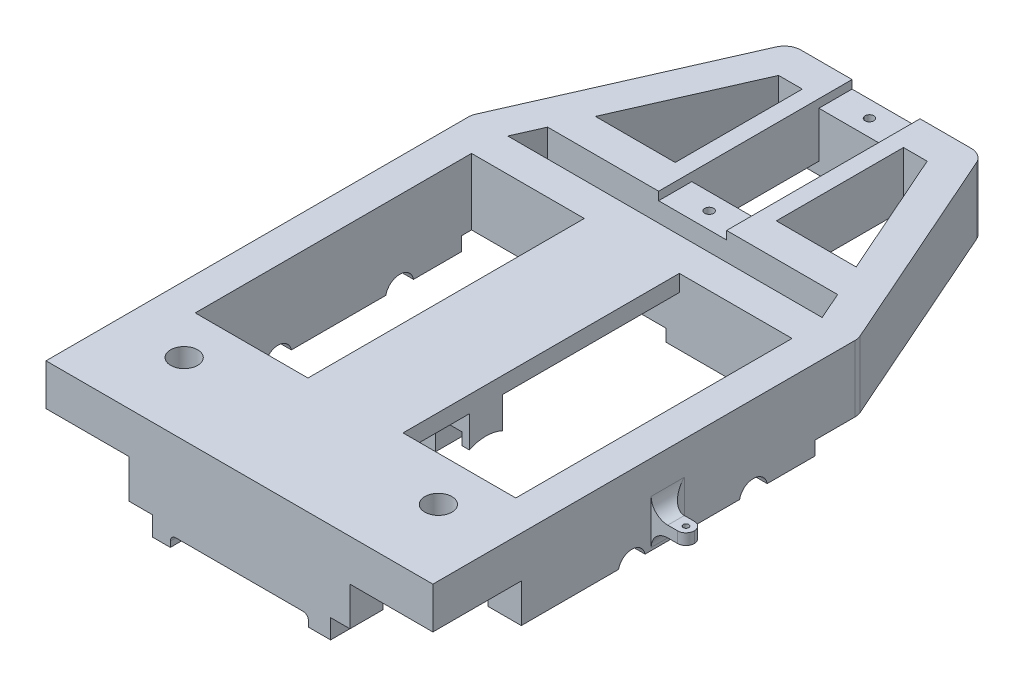
SolidWorks part; units mm, degrees
ref_plane "Front Plane" through (0, 0, 0) normal (0, 0, 1) x (1, 0, 0)
ref_plane "Top Plane" through (0, 0, 0) normal (0, 1, 0) x (1, 0, 0)
ref_plane "Right Plane" through (0, 0, 0) normal (1, 0, 0) x (0, 0, -1)
sketch "Sketch1" plane through (0, 0, 0) normal (0, 1, 0) x (1, 0, 0)
  line L0 (-35, 38.5) -> (-17.3529, 78.5)
  line L1 (-29, 32.5) -> (29, 32.5)
  line L2 (-29, 32.5) -> (-29, -32.5)
  line L3 (-29, -32.5) -> (29, -32.5)
  line L4 (29, 32.5) -> (29, -32.5)
  line L5 (-29, 32.5) -> (29, -32.5) construction
  line L6 (-29, -32.5) -> (29, 32.5) construction
  line L7 (-28.442, 38.5) -> (28.442, 38.5)
  line L8 (-35, 38.5) -> (-35, -38.5)
  line L9 (-35, -38.5) -> (35, -38.5)
  line L10 (35, 38.5) -> (35, -38.5)
  line L11 (-35, 38.5) -> (35, -38.5) construction
  line L12 (-35, -38.5) -> (35, 38.5) construction
  line L13 (-17.3529, 78.5) -> (17.3529, 78.5)
  line L14 (17.3529, 78.5) -> (35, 38.5)
  line L15 (-28.442, 38.5) -> (-13.442, 72.5)
  line L16 (-13.442, 72.5) -> (13.442, 72.5)
  line L17 (13.442, 72.5) -> (28.442, 38.5)
  point P0 (0, 0)
  point P6 (0, 0)
  point P15 (0, 72.5)
  point P18 (0, 38.5)
  dimension "D1" = 58
  dimension "D2" = 6
  dimension "D3" = 6
  dimension "D4" = 65
  dimension "D5" = 40
  dimension "D6" = 6
  dimension "D7" = 6
  dimension "D8" = 6
  dimension "D9" = 34
  dimension "D10" = 15
  dimension "D11" = 6
  dimension "D12" = 6
extrude "Boss-Extrude1" add sketch "Sketch1" along normal blind 30
ref_plane "Plane1" through (0, 0, 5.5) normal (0, 0, 1) x (1, 0, 0)
ref_plane "Plane2" through (0, 15, 0) normal (0, -1, 0) x (-1, 0, 0)
sketch "Sketch7" plane through (0, 0, -32.5) normal (0, 0, 1) x (1, 0, 0)
  line L0 (-35, 30) -> (35, 30) construction
  line L1 (-8.6, 30) -> (8.6, 30)
  line L2 (-8.6, 30) -> (-8.6, 27)
  line L3 (-8.6, 27) -> (8.6, 27)
  line L4 (8.6, 30) -> (8.6, 27)
  line L6 (-35, 30) -> (-35, 0) construction
  point P6 (0, 30)
  dimension "D1" = 3
  dimension "D2" = 17.2
  dimension "D3" = 35
sketch "Sketch8" plane through (0, 0, 5.5) normal (0, 0, 1) x (1, 0, 0)
  line L0 (-8.6, 30) -> (8.6, 30) construction
  line L1 (-8.6, 30) -> (8.6, 30)
  line L2 (-8.6, 30) -> (-8.6, 27)
  line L3 (-8.6, 27) -> (8.6, 27)
  line L4 (8.6, 30) -> (8.6, 27)
  line L5 (-8.6, 27) -> (8.6, 27) construction
sketch "Sketch9" plane through (0, 30, 0) normal (0, 1, 0) x (1, 0, 0)
  line L0 (10, 32.5) -> (2.5, -5.5)
  line L1 (-8.6, 32.5) -> (8.6, 32.5) construction
  line L2 (-8.6, -5.5) -> (8.6, -5.5) construction
  line L3 (-16.5058, -5.5) -> (16.5058, -5.5) construction
  line L4 (-10, 32.5) -> (-2.5, -5.5)
loft "Loft3" add profiles "Sketch7", "Sketch8"
mirror "Mirror3" about plane through (0, 15, 0) normal (0, -1, 0) of "Loft3"
sketch "Sketch10" plane through (0, 27, 0) normal (0, -1, 0) x (1, 0, 0)
  line L0 (-8.6, -32.5) -> (8.6, -32.5) construction
  line L1 (-2.5, 5.5) -> (2.5, 5.5)
  line L2 (-2.5, 5.5) -> (-2.5, -0.5)
  line L3 (-2.5, -0.5) -> (2.5, -0.5)
  line L4 (2.5, 5.5) -> (2.5, -0.5)
  line L6 (-8.6, 5.5) -> (8.6, 5.5) construction
  point P5 (2.5, 2.5)
  point P10 (0, 5.5)
  point P11 (0, 5.5)
  dimension "D1" = 5
  dimension "D2" = 35
  dimension "D3" = 0
  dimension "D4" = 0
extrude "Boss-Extrude3" add sketch "Sketch10" along normal up to next
sketch "Sketch2" plane through (35, 0, 0) normal (1, 0, 0) x (0, 0, -1)
  line L0 (38.5, 30) -> (38.5, 0) construction
  line L1 (-38.5, 30) -> (38.5, 30) construction
  circle A0 centre (-2.5, 15) radius 2.45
  circle A1 centre (19.5, 15) radius 2.55
  dimension "D2" = 15
  dimension "D3" = 4.9
  dimension "D5" = 5.1
  dimension "D1" = 19
  dimension "D4" = 22
extrude "Cut-Extrude1" cut sketch "Sketch2" against normal up to next
sketch "Sketch3" plane through (0, 0, -38.5) normal (0, 0, -1) x (-1, 0, 0)
  line L1 (-6.2, 20.2) -> (6.2, 20.2)
  line L2 (-6.2, 20.2) -> (-6.2, 9.8)
  line L3 (-6.2, 9.8) -> (6.2, 9.8)
  line L4 (6.2, 20.2) -> (6.2, 9.8)
  line L5 (-6.2, 20.2) -> (6.2, 9.8) construction
  line L6 (-6.2, 9.8) -> (6.2, 20.2) construction
  line L7 (-17.3529, 0) -> (17.3529, 0) construction
  line L9 (35, 30) -> (35, 0) construction
  point P0 (0, 15)
  dimension "D1" = 10.4
  dimension "D2" = 12.4
  dimension "D3" = 35
  dimension "D4" = 15
extrude "Cut-Extrude2" cut sketch "Sketch3" against normal up to next
sketch "Sketch11" plane through (35, 0, 0) normal (1, 0, 0) x (0, 0, -1)
  line L0 (-2.5, 15) -> (72.7738, 15) construction
  line L1 (1, 19) -> (4, 19)
  line L2 (1, 19) -> (1, 21)
  line L3 (1, 21) -> (4, 21)
  line L4 (4, 19) -> (4, 21)
  line L5 (4, 11) -> (4, 9)
  line L6 (1, 9) -> (4, 9)
  line L7 (1, 11) -> (1, 9)
  line L8 (1, 11) -> (4, 11)
  point P7 (2.5, 19)
  dimension "D1" = 3
  dimension "D2" = 2
  dimension "D3" = 6
  dimension "D4" = 5
extrude "Boss-Extrude4" add sketch "Sketch11" along normal blind 6.3
fillet "Fillet3" radius 1.5 4 edges at (41.3, 10, -1) (41.3, 10, -4) (41.3, 20, -1) (41.3, 20, -4)
sketch "Sketch12" plane through (0, 21, 0) normal (0, 1, 0) x (1, 0, 0)
  circle A0 centre (39.8, 2.5) radius 0.5
extrude "Cut-Extrude3" cut sketch "Sketch12" against normal through all
ref_plane "Plane3" through (0, 0, 0) normal (1, 0, 0) x (0, 0, -1)
mirror "Mirror1" about plane through (0, 0, 0) normal (1, 0, 0) of "Cut-Extrude1", "Boss-Extrude4", "Fillet3", "Cut-Extrude3"
sketch "Sketch13" plane through (-29, 0, 0) normal (1, 0, 0) x (0, 0, -1)
  line L1 (-32.5, 30) -> (-17.5, 30)
  line L2 (-32.5, 30) -> (-32.5, 24)
  line L3 (-32.5, 24) -> (-17.5, 24)
  line L4 (-17.5, 30) -> (-17.5, 24)
  dimension "D1" = 6
  dimension "D2" = 15
extrude "Boss-Extrude5" add sketch "Sketch13" along normal up to next
sketch "Sketch17" plane through (-29, 0, 0) normal (1, 0, 0) x (0, 0, -1)
  line L0 (32.5, 0) -> (-32.5, 0) construction
  line L1 (-32.5, 0) -> (-17.5, 0)
  line L2 (-32.5, 0) -> (-32.5, 14)
  line L3 (-32.5, 14) -> (-17.5, 14)
  line L4 (-17.5, 0) -> (-17.5, 14)
  dimension "D1" = 14
  dimension "D2" = 15
extrude "Boss-Extrude6" add sketch "Sketch17" along normal up to next
sketch "Sketch14" plane through (0, 30, 0) normal (0, 1, 0) x (1, 0, 0)
  line L0 (-35, 38.5) -> (-35, -38.5) construction
  line L1 (35, -38.5) -> (35, 38.5) construction
  line L2 (-35, -38.5) -> (35, -38.5) construction
  circle A0 centre (-23, -25.5) radius 2.45
  circle A1 centre (23, -25.5) radius 2.45
  dimension "D5" = 4.9
  dimension "D6" = 4.9
  dimension "D1" = 12
  dimension "D2" = 12
  dimension "D3" = 13
  dimension "D4" = 0
extrude "Cut-Extrude4" cut sketch "Sketch14" against normal through all
sketch "Sketch16" plane through (35, 0, 0) normal (1, 0, 0) x (0, 0, -1)
  line L0 (-38.5, 30) -> (-38.5, 0) construction
  line L7 (-38.5, 22.5) -> (-22.5, 22.5)
  line L8 (-38.5, 22.5) -> (-38.5, 15.5)
  line L9 (-38.5, 15.5) -> (-22.5, 15.5)
  line L10 (-22.5, 22.5) -> (-22.5, 15.5)
  line L11 (-38.5, 30) -> (38.5, 30) construction
  dimension "D1" = 7.5
  dimension "D2" = 7
  dimension "D3" = 16
extrude "Cut-Extrude7" cut sketch "Sketch16" against normal blind 15
mirror "Mirror2" about plane through (0, 0, 0) normal (1, 0, 0) of "Cut-Extrude7"
sketch "Sketch18" plane through (0, 0, 38.5) normal (0, 0, 1) x (1, 0, 0)
  line L0 (0, -16.5) -> (0, 16.5) construction
  line L3 (-35, 0) -> (35, 0) construction
  line L4 (-11.5, 14) -> (11.5, 14)
  line L5 (-11.5, 10) -> (11.5, 10)
  line L6 (-12.5, 13) -> (-12.5, 11)
  line L7 (12.5, 11) -> (12.5, 13)
  arc A2 (12.5, 11) -> (11.5, 10) centre (11.5, 11) cw
  arc A3 (12.5, 13) -> (11.5, 14) centre (11.5, 13) ccw
  arc A4 (-11.5, 10) -> (-12.5, 11) centre (-11.5, 11) cw
  arc A5 (-11.5, 14) -> (-12.5, 13) centre (-11.5, 13) ccw
  point P0 (0, 14)
  point P12 (12.5, 10)
  point P15 (12.5, 14)
  point P20 (-12.5, 14)
  dimension "D2" = 10
  dimension "D5" = 1
  dimension "D1" = 4
  dimension "D3" = 25
  dimension "D4" = 0
extrude "Cut-Extrude8" cut sketch "Sketch18" against normal up to next
sketch "Sketch19" plane through (0, 30, 0) normal (0, 1, 0) x (1, 0, 0)
  line L0 (29, -17.5) -> (-29, -17.5) construction
  line L1 (-15, -17.5) -> (15, -17.5)
  line L2 (-15, -17.5) -> (-15, -32.5)
  line L3 (-15, -32.5) -> (15, -32.5)
  line L4 (15, -17.5) -> (15, -32.5)
  line L5 (-35, -38.5) -> (35, -38.5) construction
  line L6 (-35, 38.5) -> (-35, -38.5) construction
  line L7 (35, -38.5) -> (35, 38.5) construction
  dimension "D1" = 6
  dimension "D2" = 20
  dimension "D3" = 20
extrude "Cut-Extrude9" cut sketch "Sketch19" against normal offset from surface (18 mm away) 6 from offset 6 up to face at (-23, 0, 27.95) offset against normal yes
sketch "Sketch35" plane through (0, 0, -78.5) normal (0, 0, -1) x (-1, 0, 0)
  line L0 (0, 0) -> (0, 30) construction
  line L1 (28.442, 30) -> (-28.442, 30) construction
  line L3 (-8, 18) -> (8, 18)
  line L4 (-8, 18) -> (-8, 12)
  line L5 (-8, 12) -> (8, 12)
  line L6 (8, 18) -> (8, 12)
  line L7 (-8, 18) -> (8, 12) construction
  line L8 (-8, 12) -> (8, 18) construction
  point P5 (0, 15)
  dimension "D1" = 16
  dimension "D2" = 6
extrude "Cut-Extrude18" cut sketch "Sketch35" against normal up to next
fillet "Fillet5" radius 3 6 edges at (-35, 15, -38.5) (-17.3529, 15, -78.5) (-8, 15, -78.5) (8, 15, -78.5) (17.3529, 15, -78.5) (35, 15, -38.5)
sketch "Sketch24" plane through (0, 0, 0) normal (0, 1, 0) x (1, 0, 0)
  line L0 (13.442, 72.5) -> (-13.442, 72.5) construction
  line L1 (-23.5891, 49.5) -> (-9.15, 49.5)
  line L3 (-26.2362, 43.5) -> (26.2362, 43.5)
  line L5 (28.442, 38.5) -> (13.442, 72.5) construction
  line L7 (-6.15, 49.5) -> (-6.15, 72.5)
  line L9 (6.15, 49.5) -> (6.15, 72.5)
  line L10 (-13.442, 72.5) -> (-28.442, 38.5) construction
  line L11 (26.2362, 43.5) -> (23.5891, 49.5)
  line L12 (-23.5891, 49.5) -> (-26.2362, 43.5)
  line L13 (-6.15, 49.5) -> (6.15, 49.5)
  line L15 (-9.15, 49.5) -> (-9.15, 72.5)
  line L16 (-9.15, 72.5) -> (-6.15, 72.5)
  line L17 (-6.15, 49.5) -> (-6.15, 72.5)
  line L19 (6.15, 49.5) -> (6.15, 72.5)
  line L20 (6.15, 72.5) -> (9.15, 72.5)
  line L21 (9.15, 49.5) -> (9.15, 72.5)
  line L22 (9.15, 49.5) -> (23.5891, 49.5)
  point P10 (0, 49.5)
  point P11 (-9.15, 72.5)
  point P12 (0, 43.5)
  point P13 (0, 72.5)
  point P23 (6.15, 72.5)
  point P24 (9.15, 49.5)
  dimension "D1" = 23
  dimension "D2" = 6
  dimension "D3" = 12.3
  dimension "D4" = 0
  dimension "D7" = 3
  dimension "D8" = 3
extrude "Boss-Extrude7" add sketch "Sketch24" along normal up to surface (9.8 mm away) from offset 30 contours L21 L22 L11 L3 L12 L1 L15 L16 L7 L13 L9 L20
sketch "Sketch23" plane through (0, 12, 0) normal (0, 1, 0) x (1, 0, 0)
  line L1 (-6.15, 72.5) -> (6.15, 72.5)
  line L2 (-6.15, 72.5) -> (-6.15, 78.5)
  line L3 (-6.15, 78.5) -> (6.15, 78.5)
  line L4 (6.15, 72.5) -> (6.15, 78.5)
  line L5 (15.3975, 78.5) -> (-15.3975, 78.5) construction
  line L6 (-26.2362, 43.5) -> (26.2362, 43.5) construction
  line L7 (-6.15, 49.5) -> (6.15, 49.5)
  line L8 (-6.15, 49.5) -> (-6.15, 43.5)
  line L9 (-6.15, 43.5) -> (6.15, 43.5)
  line L10 (6.15, 49.5) -> (6.15, 43.5)
  point P8 (0, 78.5)
  point P9 (0, 72.5)
  dimension "D2" = 0
extrude "Cut-Extrude12" cut sketch "Sketch23" along normal up to next from offset 16.5
sketch "Sketch26" plane through (0, 0, -38.5) normal (0, 0, -1) x (-1, 0, 0)
  line L0 (-6.2, 9.8) -> (6.2, 9.8) construction
  line L1 (6.2, 9.8) -> (6.2, 20.2) construction
  line L2 (11, 12) -> (8, 12) construction
  line L3 (-6.2, 20.2) -> (-6.2, 9.8) construction
  line L4 (-6.2, 9.8) -> (6.2, 9.8)
  line L5 (6.2, 9.8) -> (6.2, 12)
  line L7 (-6.2, 12) -> (-6.2, 9.8)
  line L8 (-11.2, 4.8) -> (11.2, 4.8)
  line L9 (11.2, 4.8) -> (11.2, 12)
  line L11 (-11.2, 12) -> (-11.2, 4.8)
  line L12 (-11.2, 12) -> (-6.2, 12)
  line L14 (6.2, 12) -> (11.2, 12)
  line L15 (-11.2, 25.2) -> (-11.2, 4.8) construction
  line L16 (11.2, 25.2) -> (-11.2, 25.2) construction
  line L17 (6.2, 20.2) -> (-6.2, 20.2) construction
  line L18 (-6.2, 20.2) -> (-6.2, 9.8) construction
  line L19 (6.2, 9.8) -> (6.2, 20.2) construction
  line L20 (11.2, 4.8) -> (11.2, 25.2) construction
  line L21 (-11, 12) -> (11, 12) construction
  dimension "D1" = 5
extrude "Boss-Extrude8" add sketch "Sketch26" along normal blind 20
sketch "Sketch28" plane through (0, 28.5, 0) normal (0, 1, 0) x (-1, 0, 0)
  line L0 (0, 16.5) -> (0, -16.5) construction
  line L1 (0.4, -44) -> (6, -44) construction
  line L2 (0.4, -78) -> (6, -78) construction
  circle A0 centre (0, -46.5) radius 0.8
  circle A1 centre (0, -75.5) radius 0.8
  dimension "D2" = 1.6
  dimension "D3" = 1.6
  dimension "D1" = 2.5
  dimension "D4" = 2.5
extrude "Cut-Extrude15" cut sketch "Sketch28" against normal up to next
fillet "Fillet4" radius 3 12 edges at (35, 9, -2.5) (35, 11, -2.5) (35, 21, -2.5) (35, 19, -2.5) (35, 20, -4) (35, 10, -4) (-35, 9, -2.5) (-35, 10, -4) (-35, 11, -2.5) (-35, 19, -2.5) (-35, 20, -4) (-35, 21, -2.5)
sketch "Sketch29" plane through (2.5, 0, 0) normal (1, 0, 0) x (0, 0, -1)
  circle A0 centre (-2.5, 15) radius 1.6
  dimension "D1" = 3.2
extrude "Cut-Extrude16" cut sketch "Sketch29" against normal up to next
sketch "Sketch30" plane through (-2.5, 0, 0) normal (-1, 0, 0) x (0, 0, 1)
  line L0 (-32.5, 27) -> (5.5, 27) construction
  line L1 (-0.5, 27) -> (5.5, 27)
  line L2 (-0.5, 27) -> (-0.5, 23.5)
  line L3 (-0.5, 23.5) -> (5.5, 23.5)
  line L4 (5.5, 27) -> (5.5, 23.5)
  line L5 (-0.5, 3) -> (-0.5, 27) construction
  line L6 (5.5, 3) -> (5.5, 27) construction
  dimension "D1" = 3.5
extrude "Boss-Extrude9" add sketch "Sketch30" along normal blind 6.1
sketch "Sketch31" plane through (0, 23.5, 0) normal (0, -1, 0) x (1, 0, 0)
  line L0 (-8.6, -0.5) -> (-2.5, -0.5) construction
  line L1 (-8.6, 5.5) -> (-7.3, 5.5)
  line L2 (-8.6, 5.5) -> (-8.6, -0.5)
  line L3 (-8.6, -0.5) -> (-7.3, -0.5)
  line L4 (-7.3, 5.5) -> (-7.3, -0.5)
  dimension "D1" = 1.3
extrude "Boss-Extrude10" add sketch "Sketch31" along normal blind 5
sketch "Sketch32" plane through (-8.6, 0, 0) normal (-1, 0, 0) x (0, 0, 1)
  line L0 (-0.5, 18.5) -> (-0.5, 21.3246)
  line L1 (-0.5, 27) -> (-0.5, 18.5) construction
  line L2 (-0.5, 18.5) -> (5.5, 18.5)
  line L3 (5.5, 18.5) -> (5.5, 21.3246)
  line L4 (5.5, 18.5) -> (5.5, 27) construction
  arc A2 (5.5, 21.3246) -> (-0.5, 21.3246) centre (2.5, 15) ccw
  dimension "D1" = 7
extrude "Cut-Extrude17" cut sketch "Sketch32" against normal up to next
mirror "Mirror4" about plane through (0, 15, 0) normal (0, -1, 0) of "Cut-Extrude17", "Boss-Extrude10", "Boss-Extrude9"
mirror "Mirror5" about plane through (0, 0, 0) normal (1, 0, 0) of "Mirror4", "Cut-Extrude17", "Boss-Extrude10", "Boss-Extrude9"
sketch "Sketch33" plane through (0, 0, 5.5) normal (0, 0, 1) x (1, 0, 0)
  line L1 (-8.6, 30) -> (8.6, 30)
  line L2 (-8.6, 30) -> (-8.6, 27)
  line L3 (-8.6, 27) -> (8.6, 27)
  line L4 (8.6, 30) -> (8.6, 27)
  dimension "D1" = 3
sketch "Sketch34" plane through (0, 0, 17.5) normal (0, 0, -1) x (-1, 0, 0)
  line L0 (-29, 30) -> (29, 30) construction
  line L1 (-8.6, 30) -> (8.6, 30)
  line L2 (-8.6, 30) -> (-8.6, 27)
  line L3 (-8.6, 27) -> (8.6, 27)
  line L4 (8.6, 30) -> (8.6, 27)
  line L5 (0, 16.5) -> (0, -16.5) construction
  point P6 (0, 27)
  dimension "D3" = 0
loft "Loft4" add profiles "Sketch33", "Sketch34"
mirror "Mirror6" about plane through (0, 15, 0) normal (0, -1, 0) of "Loft4"
sketch3d "Cut_line"
  line L0 (35, 18, -78.5) -> (35, 18, -30.637)
  line L1 (35, 15.5, 38.5) -> (35, 15.5, -30.637)
  line L2 (35, 15.5, -30.637) -> (35, 18, -30.637)
  line L3 (35, 15.5, 38.5) -> (16.4919, 15.5, 38.5)
  line L4 (12.5, 12, 38.5) -> (16.4919, 12, 38.5)
  line L5 (12.5, 11, 38.5) -> (12.5, 13, 38.5) construction
  line L6 (16.4919, 12, 38.5) -> (16.4919, 15.5, 38.5)
  line L7 (12.5, 12, 38.5) -> (-15.6959, 12, 38.5)
  line L8 (-15.6959, 12, 38.5) -> (-15.6959, 15.5, 38.5)
  line L9 (-15.6959, 15.5, 38.5) -> (-35, 15.5, 38.5)
  line L10 (35, 18, -78.5) -> (-35, 18, -78.5)
  line L11 (-35, 18, -78.5) -> (-35, 18, -30.637)
  line L12 (-35, 18, -30.637) -> (-35, 15.5, -30.637)
  line L13 (-35, 15.5, -30.637) -> (-35, 15.5, 38.5)
  line L14 (-11, 18, -78.5) -> (11, 18, -78.5) construction
  dimension "D1" = 0
sketch "Sketch36" plane through (0, 0, 0) normal (0, -1, 0) x (1, 0, 0)
  line L1 (-61.4126, 50.2931) -> (56.2353, 50.2931)
  line L2 (-61.4126, 50.2931) -> (-61.4126, -80.0736)
  line L3 (-61.4126, -80.0736) -> (56.2353, -80.0736)
  line L4 (56.2353, 50.2931) -> (56.2353, -80.0736)
extrude "Cut-Extrude19" cut sketch "Sketch36" against normal blind 12
sketch "Sketch37" plane through (0, 12, 0) normal (0, -1, 0) x (1, 0, 0)
  line L0 (29, 32.5) -> (-29, 32.5) construction
  line L1 (-52.1916, 45.5236) -> (70.2259, 45.5236)
  line L2 (-52.1916, 45.5236) -> (-52.1916, -90.2485)
  line L3 (-52.1916, -90.2485) -> (70.2259, -90.2485)
  line L4 (70.2259, 45.5236) -> (70.2259, -90.2485)
  line L5 (-15.6959, 38.5) -> (16.4919, 38.5)
  line L6 (-15.6959, 38.5) -> (-15.6959, 32.5)
  line L7 (-15.6959, 32.5) -> (16.4919, 32.5)
  line L8 (16.4919, 38.5) -> (16.4919, 32.5)
extrude "Cut-Extrude20" cut sketch "Sketch37" against normal blind 3.5
sketch "Sketch38" plane through (0, 15.5, 0) normal (0, -1, 0) x (1, 0, 0)
  line L1 (-35, -30.637) -> (35, -30.637)
  line L2 (-35, -30.637) -> (-35, -78.5)
  line L3 (-35, -78.5) -> (35, -78.5)
  line L4 (35, -30.637) -> (35, -78.5)
  line L5 (-2.5, 5.5) -> (2.5, 5.5)
  line L6 (-2.5, 5.5) -> (-2.5, -0.5)
  line L7 (-2.5, -0.5) -> (2.5, -0.5)
  line L8 (2.5, 5.5) -> (2.5, -0.5)
extrude "Cut-Extrude21" cut sketch "Sketch38" against normal blind 2.5
sketch "Sketch39" plane through (0, 18, 0) normal (0, -1, 0) x (1, 0, 0)
  line L0 (-2.5, 2.5) -> (2.5, 2.5) construction
  line L1 (-2.5, 5.5) -> (-2.5, -0.5) construction
  line L2 (2.5, -0.5) -> (2.5, 5.5) construction
  line L3 (-8.6, 5.5) -> (8.6, 5.5) construction
  line L4 (-1.3, 3.9) -> (1.3, 3.9)
  line L5 (-1.3, 3.9) -> (-1.3, 1.1)
  line L6 (-1.3, 1.1) -> (1.3, 1.1)
  line L7 (1.3, 3.9) -> (1.3, 1.1)
  line L8 (-1.3, 3.9) -> (1.3, 1.1) construction
  line L9 (-1.3, 1.1) -> (1.3, 3.9) construction
  point P6 (0, 2.5)
  dimension "D1" = 1.6
  dimension "D2" = 1.2
extrude "Cut-Extrude22" cut sketch "Sketch39" against normal blind 1.5
